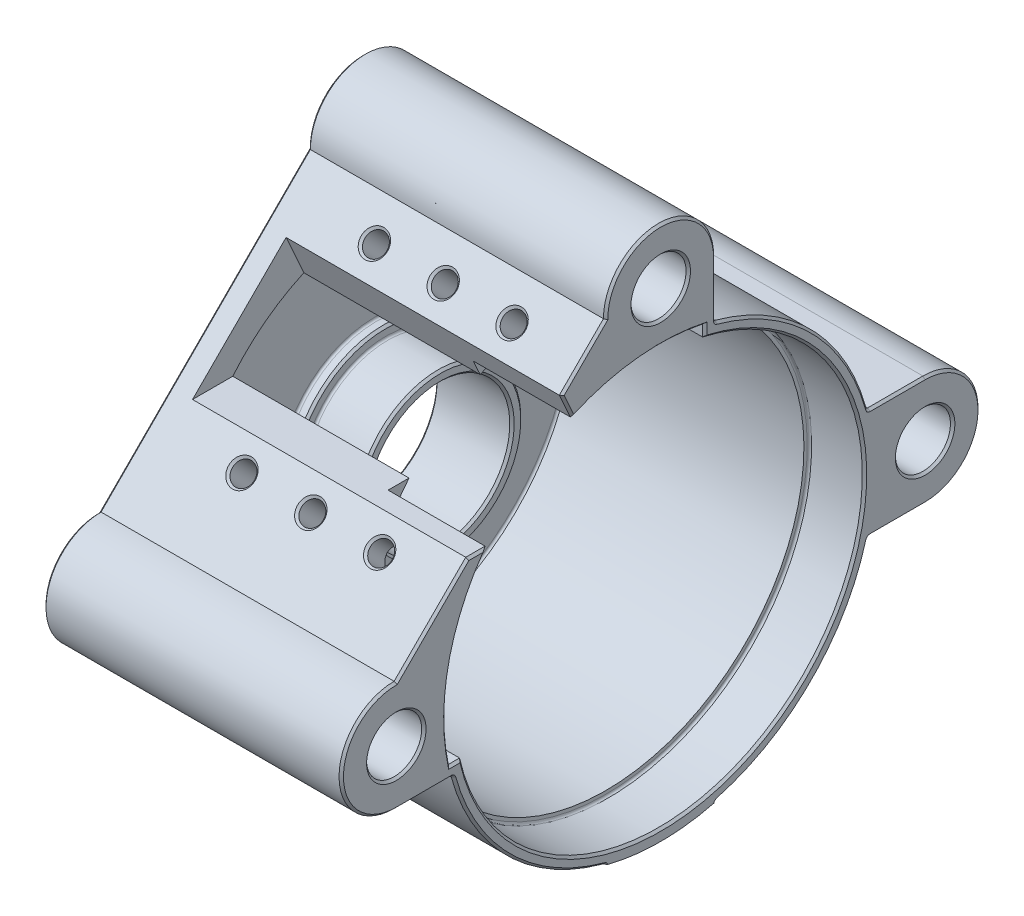
SolidWorks part; units mm, degrees
material "1060 Сплав"
ref_plane "Спереди" through (0, 0, 0) normal (0, 0, 1) x (1, 0, 0)
ref_plane "Сверху" through (0, 0, 0) normal (0, 1, 0) x (1, 0, 0)
ref_plane "Справа" through (0, 0, 0) normal (1, 0, 0) x (0, 0, -1)
sketch "Эскиз1" plane through (0, 0, 0) normal (0, 0, 1) x (1, 0, 0)
  line L0 (0, 0) -> (26039.5549, 0) construction
  line L1 (-25, 7.5) -> (-25, 8.5)
  line L2 (0, 19.5) -> (-27, 19.5)
  line L3 (-27, 19.5) -> (-27, 6.5)
  line L4 (-27, 6.5) -> (-20, 6.5)
  line L5 (-20, 6.5) -> (-20, 7.5)
  line L6 (-20, 7.5) -> (-25, 7.5)
  line L7 (-26, 8.5) -> (-26, 18)
  line L8 (-26, 18) -> (-5, 18)
  line L9 (-5, 18) -> (-5, 18.5)
  line L10 (-5, 18.5) -> (0, 18.5)
  line L11 (0, 18.5) -> (0, 19.5)
  line L12 (-25, 8.5) -> (-26, 8.5)
  dimension "D1" = 18.5
  dimension "D2" = 1
  dimension "D3" = 18
  dimension "D4" = 5
  dimension "D5" = 21
  dimension "D6" = 1
  dimension "D7" = 1
  dimension "D8" = 1
  dimension "D9" = 7.5
  dimension "D10" = 1
  dimension "D11" = 13
  dimension "D12" = 0.5
  dimension "D13" = 5
revolve "Повернуть1" add sketch "Эскиз1" angle 360 about L0
sketch "Эскиз5" plane through (0, 0, 0) normal (1, 0, 0) x (0, 0, -1)
  line L0 (0, 0) -> (0, -24) construction
  line L1 (5, -24) -> (5, -18.8481)
  line L2 (-5, -24) -> (-5, -18.8481)
  line L3 (-24, -5) -> (-18.8481, -5)
  line L5 (0, 0) -> (-24, 0) construction
  line L7 (5, 24) -> (5, 18.8481)
  line L8 (0, 0) -> (0, 24) construction
  line L9 (24, 5) -> (18.8481, 5)
  line L10 (24, -5) -> (18.8481, -5)
  line L11 (0, 0) -> (24, 0) construction
  line L12 (-24, 5) -> (-5, 24)
  line L14 (-24, 5) -> (-18.8481, 5) [skipped]
  line L15 (-5, 24) -> (-5, 18.8481) [skipped]
  circle A0 centre (0, -24) radius 2.5
  arc A1 (5, -24) -> (-5, -24) centre (0, -24) cw
  arc A2 (5, -18.8481) -> (-5, -18.8481) centre (0, 0) cw
  circle A3 centre (0, 0) radius 19.5 construction
  circle A5 centre (-24, 0) radius 2.5
  arc A6 (-24, -5) -> (-24, 5) centre (-24, 0) cw
  arc A7 (-18.8481, -5) -> (-5, 18.8481) centre (0, 0) cw
  circle A8 centre (0, 24) radius 2.5
  arc A9 (-5, 24) -> (5, 24) centre (0, 24) cw
  arc A10 (-5, 18.8481) -> (5, 18.8481) centre (0, 0) cw
  circle A11 centre (24, 0) radius 2.5
  arc A12 (24, 5) -> (24, -5) centre (24, 0) cw
  arc A13 (18.8481, 5) -> (18.8481, -5) centre (0, 0) cw
  point P32 (0, 0)
  dimension "D2" = 5
  dimension "D3" = 5
  dimension "D4" = 19.5
  dimension "D1" = 24
  dimension "D5" = 5.1519
  dimension "D6" = 5.1519
  dimension "D7" = 4
extrude "Бобышка-Вытянуть2" add sketch "Эскиз5" against normal through all
sketch "Эскиз2" plane through (0, 0, 0) normal (1, 0, 0) x (0, 0, -1)
  line L0 (0, 0) -> (0, 50000) construction
  line L1 (4, 19.0853) -> (4, 16.5227)
  line L2 (4, 0) -> (4, 50000) construction
  line L3 (0, 0) -> (0, -4) construction
  line L4 (0, -4) -> (-50000, -4) construction
  line L5 (-19.0853, -4) -> (-16.5227, -4)
  line L6 (-4, 0) -> (-4, 50000) construction
  arc A0 (4, 16.5227) -> (-16.5227, -4) centre (0, 0) ccw
  arc A1 (-19.0853, -4) -> (4, 19.0853) centre (0, 0) cw
  circle A2 centre (0, 0) radius 19.5 construction
  dimension "D3" = 17
  dimension "D4" = 19.5
  dimension "D1" = 4
  dimension "D2" = 4
  dimension "D5" = 2.5626
  dimension "D6" = 2.5626
  dimension "D7" = 16.5227
extrude "Вырез-Вытянуть1" cut sketch "Эскиз2" against normal blind 9 contours A0 L5 A1 L1
sketch "Эскиз3" plane through (0, 0, 0) normal (1, 0, 0) x (0, 0, -1)
  line L3 (-40, 11.5) -> (-12.52, 11.5)
  line L4 (0, 0) -> (-20535.6471, 45588.2353) construction
  line L5 (-6.9821, 15.5) -> (-13.2408, 29.394)
  line L6 (-13.2408, 29.394) -> (-40, 11.5)
  line L7 (0, 15.5) -> (-50000, 15.5) construction
  circle A0 centre (0, 0) radius 15.5 construction
  circle A1 centre (0, 0) radius 11.5 construction
  arc A2 (-6.9821, 15.5) -> (-12.52, 11.5) centre (0, 0) ccw
  dimension "D1" = 31
  dimension "D2" = 23
  dimension "D4" = 34
  dimension "D3" = 15.2386
  dimension "D5" = 32.1908
extrude "Вырез-Вытянуть2" cut sketch "Эскиз3" against normal blind 25
sketch "Эскиз6" plane through (0, 14.5, 14.5) normal (0, 0.7071, 0.7071) x (1, 0, 0)
  line L0 (-25, -4.2426) -> (0, 7.7692) construction
  line L1 (-12.5, 1.7633) -> (-50012.5, 1.7633) construction
  circle A0 centre (-18.75, 10.2633) radius 1
  circle A1 centre (-12.5, 10.2633) radius 1
  circle A2 centre (-6.25, 10.2633) radius 1
  circle A3 centre (-6.25, -6.7367) radius 1
  circle A4 centre (-12.5, -6.7367) radius 1
  circle A5 centre (-18.75, -6.7367) radius 1
  point P6 (-12.5, 1.7633)
  dimension "D2" = 2
  dimension "D5" = 6.25
  dimension "D1" = 8.5
  dimension "D3" = 18.75
  dimension "D4" = 3
extrude "Вырез-Вытянуть4" cut sketch "Эскиз6" against normal blind 10
fillet "Скругление1" radius 0.2 10 edges at (-13.5, -5, 18.8481) (-13.5, -18.8481, 5) (-13.5, -18.8481, -5) (-13.5, -5, -18.8481) (-13.5, 18.8481, -5) (-13.5, 5, -18.8481) (-5, -13.0815, -13.0815) (-25, 0, 7.5) (-26, 0, 8.5) (-26, 0, 18)
chamfer "Фаска1" distance 0.2 angle 45 60 edges at (-27, 0, -26.5) (-27, 0, 21.5) (-27, 24, -2.5) (-27, -24, -2.5) (-27, -29, 0) (-27, -21.5007, -5) (-27, -18.88, -5.041) (-27, -13.7886, -13.7886) (-27, -5.041, -18.88) (-27, -5, -21.5007) (-27, 0, -29) (-27, 5, -21.5007) (-27, 5.041, -18.88) (-27, 13.7886, -13.7886) (-27, 18.88, -5.041) (-27, 21.5007, -5) (-27, 29, 0) (-27, 14.5, 14.5) (-27, 0, 29) (-27, -5, 21.5007) (-27, -5.041, 18.88) (-27, -13.7886, 13.7886) (-27, -18.88, 5.041) (-27, -21.5007, 5) (-27, 0, 6.5) (-20, 0, 6.5) (-20, 0, 7.5) (0, 0, -26.5) (0, 0, 21.5) (0, 24, -2.5) (0, -24, -2.5) (0, 29, 0) (0, 21.5007, -5) (0, 18.88, -5.041) (0, 13.7886, -13.7886) (0, 5.041, -18.88) (0, 5, -21.5007) (0, 0, -29) (0, -5, -21.5007) (0, -5.041, -18.88) (0, -13.7886, -13.7886) (0, -18.88, -5.041) (0, -21.5007, -5) (0, -29, 0) (0, -21.5007, 5) (0, -18.88, 5.041) (0, -13.7886, 13.7886) (0, -5.041, 18.88) (0, -5, 21.5007) (0, 0, 29) (0, 8.25, 20.75) (0, 11.5, 16.624) (0, 4.1045, 19.0631) (0, -4, 18.5739) (0, -13.0815, -13.0815) (0, 18.5739, -4) (0, 19.3857, 2.1081) (0, 18.8865, 8.5076) (0, 21.9968, 7.0032) (-25, 0, 8.5)
chamfer "Фаска2" distance 0.2 angle 45 6 edges at (-6.25, 21.0501, 7.9499) (-12.5, 21.0501, 7.9499) (-18.75, 21.0501, 7.9499) (-18.75, 10.4435, 18.5565) (-12.5, 10.4435, 18.5565) (-6.25, 10.4435, 18.5565)
sketch "Эскиз7" plane through (-27, 0, 0) normal (-1, 0, 0) x (0, 0, 1)
  line L0 (0, 0) -> (0, -50000) construction
  line L1 (0, 0) -> (-25000, -43301.2702) construction
  line L2 (0, 0) -> (25000, -43301.2702) construction
  line L3 (-9.75, -16.8875) -> (-20, -34.641)
  line L4 (-20, -34.641) -> (20, -34.641)
  line L5 (20, -34.641) -> (9.75, -16.8875)
  arc A0 (-9.75, -16.8875) -> (9.75, -16.8875) centre (0, 0) ccw
  arc A1 (9.75, 16.8875) -> (-9.75, 16.8875) centre (0, 0) ccw
  circle M11 centre (0, -24) radius 2.7
  line M12 (-4.8, -19.0013) -> (-4.8, -24)
  arc M13 (-4.8, -24) -> (4.8, -24) centre (0, -24) ccw
  line M14 (4.8, -24) -> (4.8, -19.0013)
  arc M15 (4.8, -19.0013) -> (5.0944, -18.6155) centre (5.2, -19.0013) cw
  arc M31 (-5.0944, -18.6155) -> (-4.8, -19.0013) centre (-5.2, -19.0013) cw
  dimension "D1" = 39
  dimension "D2" = 60
  dimension "D3" = 30
  dimension "D4" = 40
  dimension "D5" = 60
  dimension "D6" = 60
extrude "Вырез-Вытянуть6" cut sketch "Эскиз7" against normal through all contours A0 M31 M12 M13 M14 M15 M11 | A0 L3 L4 L5 M15 M14 M13 M12 M31 | M11 region at (-27, -18.4667, -7.5159) region at (-27, -19.6381, 0) region at (-27, -24, 0)
